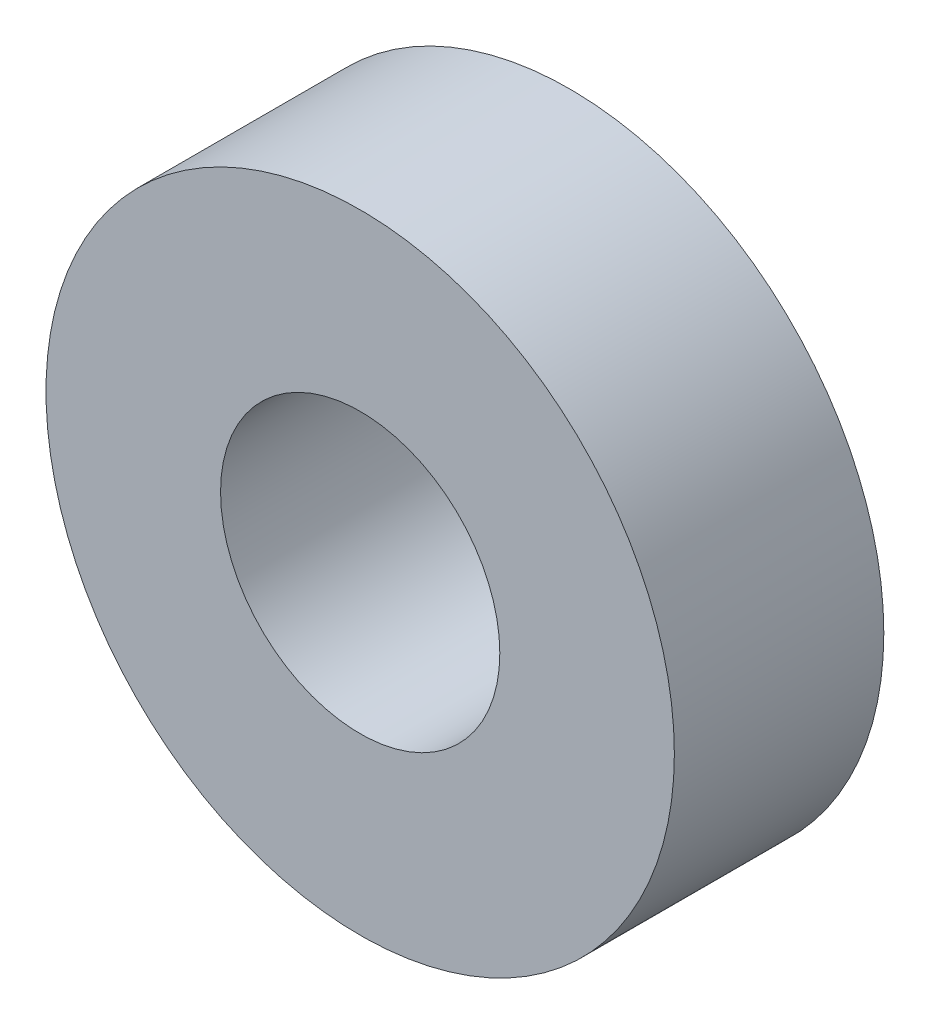
SolidWorks part; units mm, degrees
material "Brass"
ref_plane "Front Plane" through (0, 0, 0) normal (0, 0, 1) x (1, 0, 0)
ref_plane "Top Plane" through (0, 0, 0) normal (0, 1, 0) x (1, 0, 0)
ref_plane "Right Plane" through (0, 0, 0) normal (1, 0, 0) x (0, 0, -1)
sketch "Sketch1" plane through (0, 0, 0) normal (0, 0, 1) x (1, 0, 0)
  circle A0 centre (0, 0) radius 4
  circle A1 centre (0, 0) radius 9
  dimension "D1" = 8
  dimension "D2" = 5
extrude "Boss-Extrude1" add sketch "Sketch1" along normal blind 3 and the other way blind 3
ref_plane "Plane1" through (0, 0, 0) normal (-0.7071, 0, 0.7071) x (0.7071, 0, 0.7071)
sketch "Sketch4" plane through (0, 0, 0) normal (-0.7071, 0, 0.7071) x (0.7071, 0, 0.7071)
  circle A0 centre (0, 0) radius 6.4353
  dimension "D1" = 12.8706
